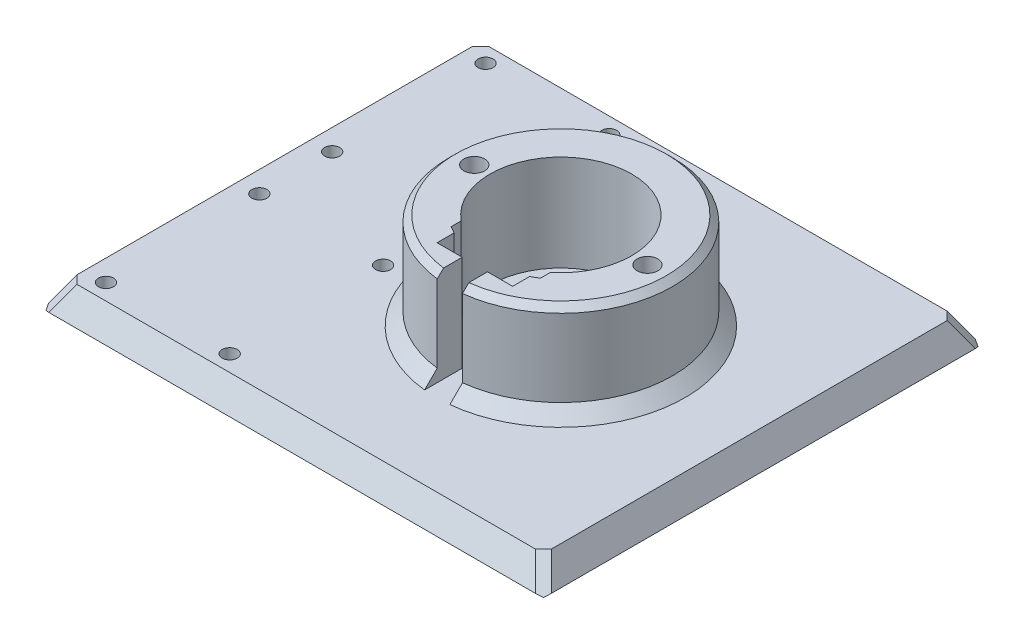
SolidWorks part; units mm, degrees
material "ABS"
ref_plane "Front Plane" through (0, 0, 0) normal (0, 0, 1) x (1, 0, 0)
ref_plane "Top Plane" through (0, 0, 0) normal (0, 1, 0) x (1, 0, 0)
ref_plane "Right Plane" through (0, 0, 0) normal (1, 0, 0) x (0, 0, -1)
sketch "Sketch1" plane through (0, 0, 0) normal (0, 1, 0) x (1, 0, 0)
  line L1 (-57.8485, 41.6242) -> (38.1, 41.6242)
  line L2 (-57.8485, 41.6242) -> (-57.8485, -41.6242)
  line L3 (-57.8485, -41.6242) -> (38.1, -41.6242)
  line L4 (38.1, 41.6242) -> (38.1, -41.6242)
  circle A0 centre (0, 0) radius 14.3192
  circle A1 centre (0, 0) radius 22.5742
  circle A2 centre (-17.5, 0) radius 2.0955
  circle A4 centre (17.5, 0) radius 2.0955
  arc A7 (17.5, -2) -> (17.5, 2) centre (17.5, 0) ccw construction
  arc A8 (-17.5, -2) -> (-17.5, 2) centre (-17.5, 0) ccw construction
  point P9 (-57.8485, 0)
  dimension "D1" = 28.6385
  dimension "D2" = 45.1485
  dimension "D5" = 4.191
  dimension "D3" = 83.2485
  dimension "D4" = 95.9485
  dimension "D10" = 38.1
extrude "Boss-Extrude1" add sketch "Sketch1" along normal blind 19.431 contours A1 A0 region at (-21.9358, 0, 0)
sketch "Sketch2" plane through (0, 0, 0) normal (0, -1, 0) x (1, 0, 0)
  line L0 (38.1, -41.6242) -> (38.1, 41.6242) construction
  line L1 (-57.8485, -41.6242) -> (38.1, -41.6242) construction
  line L2 (-57.8485, -41.6242) -> (-57.8485, 41.6242) construction
  line L3 (-57.8485, 41.6242) -> (38.1, 41.6242) construction
  line L4 (38.1, -41.6242) -> (38.1, 41.6242)
  line L5 (-57.8485, -41.6242) -> (38.1, -41.6242)
  line L6 (-57.8485, -41.6242) -> (-57.8485, 41.6242)
  line L7 (-57.8485, 41.6242) -> (38.1, 41.6242)
extrude "Boss-Extrude2" add sketch "Sketch2" along normal blind 6.35 draft 30 draft outward yes
sketch "Sketch3" plane through (0, 19.431, 0) normal (0, 1, 0) x (1, 0, 0)
  line L2 (-2.5544, -17.3828) -> (-2.5544, -22.7168)
  line L10 (-9.017, -13.1556) -> (-7.6344, -13.9538)
  line L11 (-7.6344, -13.9538) -> (-7.6344, -17.3828)
  line L12 (0, -11.1236) -> (0, -22.86) construction
  line L13 (-9.017, -11.1236) -> (9.017, -11.1236)
  line L14 (-7.6344, -17.3828) -> (-2.5544, -17.3828)
  line L15 (-9.017, -13.1556) -> (-9.017, -11.1236)
  line L16 (2.5544, -17.3828) -> (2.5544, -22.7168)
  line L17 (7.6344, -17.3828) -> (2.5544, -17.3828)
  line L18 (7.6344, -13.9538) -> (7.6344, -17.3828)
  line L19 (9.017, -13.1556) -> (7.6344, -13.9538)
  line L20 (9.017, -13.1556) -> (9.017, -11.1236)
  circle A0 centre (0, 0) radius 14.3192 construction
  arc A1 (-2.5544, -22.7168) -> (0, -22.86) centre (-0.1246, -2.2229) ccw
  circle A2 centre (0, 0) radius 22.86 construction
  arc A3 (2.5544, -22.7168) -> (0, -22.86) centre (0.1246, -2.2229) cw
  dimension "D1" = 45.72
  dimension "D8" = 20.6375
  dimension "D2" = 60
  dimension "D3" = 2.032
  dimension "D4" = 3.429
  dimension "D5" = 5.08
  dimension "D6" = 5.334
  dimension "D7" = 9.017
extrude "Cut-Extrude1" cut sketch "Sketch3" against normal up to surface (19.431 mm away) up to face at (0, 0, 22.5742)
fillet "Fillet1" radius 1.27 1 edges at (0, 19.431, -22.5742) profile chamfer
fillet "Fillet3" radius 1.905 4 edges at (-59.6816, -3.175, -43.4573) (39.9331, -3.175, -43.4573) (39.9331, -3.175, 43.4573) (-59.6816, -3.175, 43.4573) profile chamfer
chamfer "Chamfer2" distance 1.651 angle 79 8 edges at (41.7662, -6.35, 0) (-61.5147, -6.35, 0) (-60.6898, -6.35, -44.4655) (-60.6898, -6.35, 44.4655) (-9.8742, -6.35, -45.2904) (-9.8742, -6.35, 45.2904) (40.9413, -6.35, -44.4655) (40.9413, -6.35, 44.4655) first distance on face at (39.9331, -3.175, 0) first distance on face at (-59.6816, -3.175, 0) first distance on face at (-58.8567, -3.175, -42.6324) first distance on face at (-58.8567, -3.175, 42.6324) first distance on face at (-9.8742, -3.175, -43.4573) first distance on face at (-9.8742, -3.175, 43.4573) first distance on face at (39.1082, -3.175, -42.6324) first distance on face at (39.1082, -3.175, 42.6324)
sketch "Sketch6" plane through (0, 0, 0) normal (0, 1, 0) x (1, 0, 0)
  circle A0 centre (-53.5785, -7.3542) radius 1.524
  circle A1 centre (-28.5785, -7.3542) radius 1.524
  circle A2 centre (-28.5785, -38.3542) radius 1.524
  circle A3 centre (-53.5785, -38.3542) radius 1.524
  circle A4 centre (-28.5785, 7.3542) radius 1.524
  circle A5 centre (-53.5785, 7.3542) radius 1.524
  circle A6 centre (-28.5785, 38.3542) radius 1.524
  circle A7 centre (-53.5785, 38.3542) radius 1.524
  circle A9 centre (-17.5, 0) radius 2.0955 construction
  circle A10 centre (17.5, 0) radius 2.0955 construction
  circle A11 centre (-17.5, 0) radius 2.0955
  circle A12 centre (17.5, 0) radius 2.0955
  dimension "D1" = 3.048
extrude "Cut-Extrude2" cut sketch "Sketch6" against normal up to surface (6.35 mm away) up to face at (-9.8742, -6.35, 0)
chamfer "Chamfer3" distance 2.54 angle 45 1 edges at (0, 0, -22.5742)
sketch "Sketch7" plane through (0, -6.35, 0) normal (0, -1, 0) x (1, 0, 0)
  circle A0 centre (-17.5, 0) radius 6.35
  circle A1 centre (17.5, 0) radius 6.35
  dimension "D1" = 12.7
extrude "Cut-Extrude3" cut sketch "Sketch7" against normal blind 0.9
equation "\"D3@Sketch1\"=\"D2@Sketch1\"+1.5"
equation "\"D2@Sketch1\"=\"D1@Sketch1\"+0.65"
equation "\"D4@Sketch1\"=\"D2@Sketch1\"+2"
